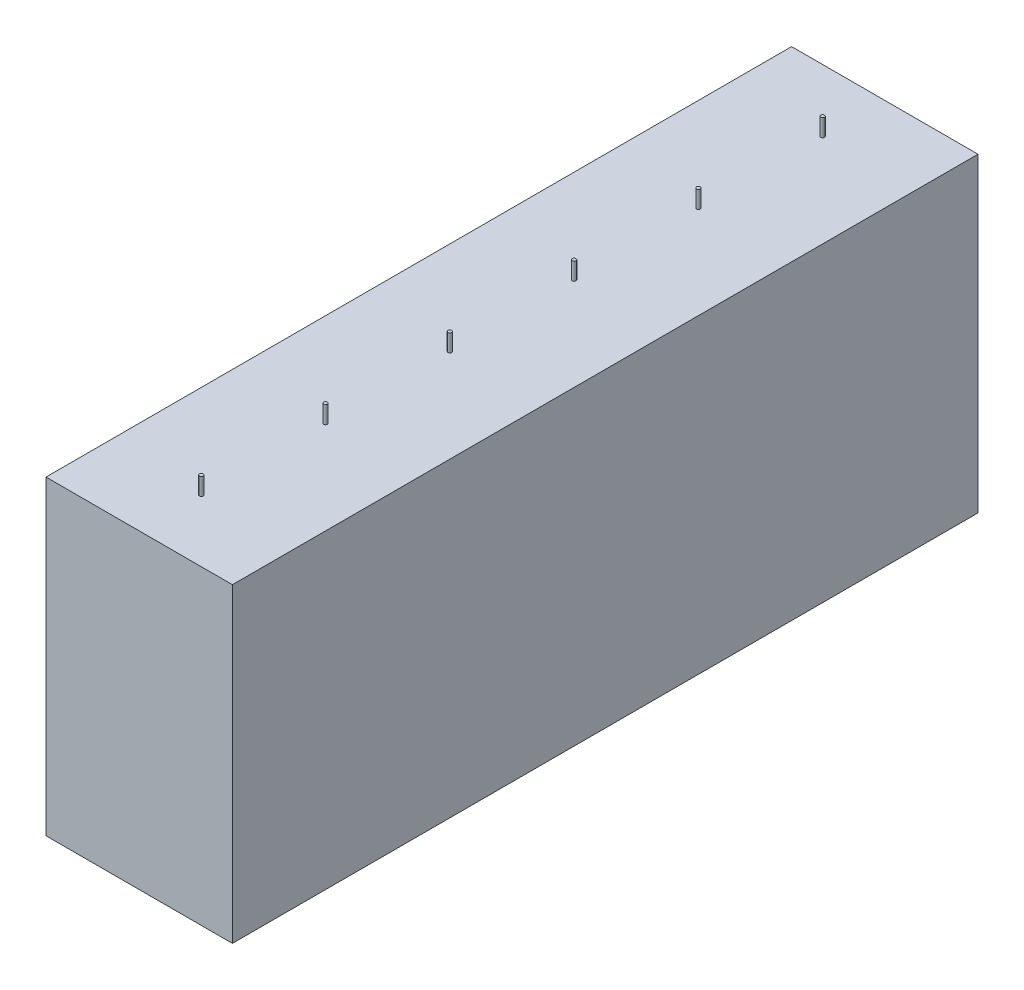
SolidWorks part; units mm, degrees
ref_plane "前视基准面" through (0, 0, 0) normal (0, 0, 1) x (1, 0, 0)
ref_plane "上视基准面" through (0, 0, 0) normal (0, 1, 0) x (1, 0, 0)
ref_plane "右视基准面" through (0, 0, 0) normal (1, 0, 0) x (0, 0, -1)
other "Configuration Table"
sketch "草图1" plane through (0, 0, 0) normal (0, 1, 0) x (1, 0, 0)
  line L1 (-150, -600) -> (150, -600)
  line L2 (-150, -600) -> (-150, 600)
  line L3 (-150, 600) -> (150, 600)
  line L4 (150, -600) -> (150, 600)
  line L5 (-150, -600) -> (150, 600) construction
  line L6 (-150, 600) -> (150, -600) construction
  point P0 (0, 0)
  dimension "D1" = 300
  dimension "D2" = 1200
extrude "凸台-拉伸1" add sketch "草图1" along normal blind 500
sketch "草图2" plane through (0, 500, 0) normal (0, 1, 0) x (1, 0, 0)
  line L0 (0, 600) -> (0, 500) construction
  line L1 (150, 600) -> (-150, 600) construction
  line L2 (0, 500) -> (0, 300) construction
  line L3 (0, 300) -> (0, 100) construction
  line L4 (0, 100) -> (0, -100) construction
  line L5 (0, -100) -> (0, -300) construction
  line L6 (0, -300) -> (0, -500) construction
  line L7 (0, -500) -> (0, -600) construction
  line L8 (-150, -600) -> (150, -600) construction
  circle A0 centre (0, 500) radius 3
  circle A1 centre (0, 300) radius 3
  circle A2 centre (0, 100) radius 3
  circle A3 centre (0, -100) radius 3
  circle A4 centre (0, -300) radius 3
  circle A5 centre (0, -500) radius 3
  dimension "D2" = 6
  dimension "D1" = 200
extrude "凸台-拉伸2" add sketch "草图2" along normal blind 28
sketch "草图4" plane through (0, 0, 600) normal (0, 0, 1) x (1, 0, 0)
  line L0 (-150, 0) -> (150, 0) construction
  line L1 (-25, 0) -> (25, 0)
  line L2 (-25, 0) -> (-25, 100)
  line L3 (-25, 100) -> (25, 100)
  line L4 (25, 0) -> (25, 100)
  dimension "D1" = 50
  dimension "D2" = 100
  dimension "D3" = 25
